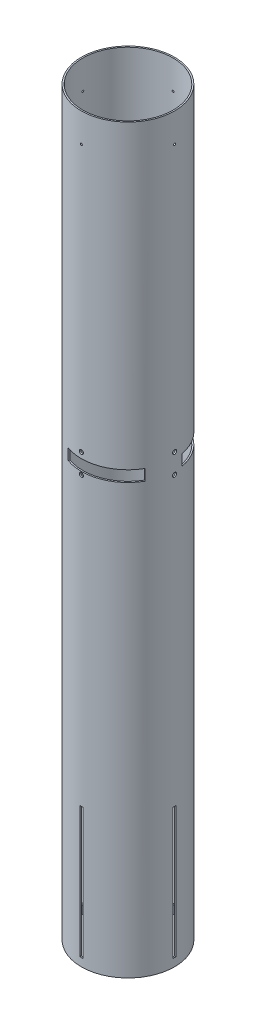
SolidWorks part; units mm, degrees
material "A-Glass Fiber"
ref_plane "Front Plane" through (0, 0, 0) normal (0, 0, 1) x (1, 0, 0)
ref_plane "Top Plane" through (0, 0, 0) normal (0, 1, 0) x (1, 0, 0)
ref_plane "Right Plane" through (0, 0, 0) normal (1, 0, 0) x (0, 0, -1)
sketch "Sketch1" plane through (0, 0, 0) normal (0, 1, 0) x (1, 0, 0)
  circle A0 centre (0, 0) radius 49.53
  circle A1 centre (0, 0) radius 51.1048
  dimension "D1" = 99.06
  dimension "D2" = 102.2096
extrude "Boss-Extrude1" add sketch "Sketch1" along normal blind 812.8
ref_plane "Plane1" through (0, 0, 0) normal (0.7071, 0, 0.7071) x (0.7071, 0, -0.7071)
ref_axis "Axis1" through (0, 812.8, 0) along (0, -1, 0)
sketch "Sketch2" plane through (0, 0, 0) normal (1, 0, 0) x (0, 0, -1)
  line L0 (0, 0) -> (0, 8.89)
  line L1 (1.5875, 8.89) -> (-1.5875, 8.89)
  line L2 (1.5875, 8.89) -> (1.5875, 152.4)
  line L3 (1.5875, 152.4) -> (-1.5875, 152.4)
  line L4 (-1.5875, 8.89) -> (-1.5875, 152.4)
  line L5 (1.5875, 8.89) -> (-1.5875, 152.4) construction
  line L6 (1.5875, 152.4) -> (-1.5875, 8.89) construction
  line L7 (51.1048, 812.8) -> (-51.1048, 812.8) construction
  line L8 (51.1048, 812.8) -> (-51.1048, 812.8)
  line L9 (0, 812.8) -> (0, 488.95)
  line L10 (-51.1048, 0) -> (51.1048, 0) construction
  circle A0 centre (0, 488.95) radius 2.25
  point P0 (0, 80.645)
  dimension "D4" = 4.5
  dimension "D1" = 3.175
  dimension "D5" = 488.95
  dimension "D3" = 152.4
  dimension "D2" = 8.89
extrude "Cut-Extrude1" cut sketch "Sketch2" against normal through all contours L4 L1 L2 L3 region at (0, 80.645, 0)
pattern_circular "CirPattern1" count 4 over 360 about axis through (0, 0, 0) along (0, 1, 0) of "Cut-Extrude1" reverse direction yes
extrude "Cut-Extrude2" cut sketch "Sketch2<3>" against normal through all contours A0 region at (0, 487.404, 1.546)
sketch "Sketch2<3>" plane through (0, 0, 0) normal (1, 0, 0) x (0, 0, -1) same geometry as "Sketch2"
pattern_circular "CirPattern2" count 4 over 360 about axis through (0, 812.8, 0) along (0, -1, 0) of "Cut-Extrude2"
sketch "Sketch3" plane through (0, 0, 0) normal (0.7071, 0, 0.7071) x (0.7071, 0, -0.7071)
  line L0 (0, 0) -> (0, 127) construction
  circle A0 centre (0, 127) radius 3.175
  dimension "D1" = 6.35
  dimension "D2" = 127
extrude "Cut-Extrude3" cut sketch "Sketch3" against normal through all
sketch "Sketch7" plane through (0, 0, 0) normal (0, 1, 0) x (1, 0, 0)
  line L0 (0, 0) -> (-44.2581, -25.5524)
  line L1 (0, 0) -> (0, 93.232) construction
  line L2 (0, 0) -> (-32.8495, 39.1485)
  line L3 (-51.1048, 0) -> (0, 0) construction
  arc A0 (-51.0552, 2.25) -> (-51.0552, -2.25) centre (0, 0) ccw construction
  circle A1 centre (0, 0) radius 49.53 construction
  circle A2 centre (0, 0) radius 51.1048
  circle A3 centre (0, 0) radius 51.1048
  circle A4 centre (0, 0) radius 49.53
  circle A5 centre (0, 0) radius 51.1048 construction
  arc A6 (2.25, 51.0552) -> (-2.25, 51.0552) centre (0, 0) ccw construction
  arc A7 (-51.0552, 2.25) -> (-51.0552, -2.25) centre (0, 0) ccw
  arc A8 (2.25, 51.0552) -> (-2.25, 51.0552) centre (0, 0) ccw
  dimension "D1" = 80
  dimension "D3" = 30
  dimension "D2" = 0
extrude "Cut-Extrude4" cut sketch "Sketch7" against normal blind 12.065 from offset 482.6 contours A4 A3 L0 region at (-43.9137, 0, 24.5741)
pattern_circular "CirPattern3" count 3 over 360 about axis through (0, 812.8, 0) along (0, -1, 0) of "Cut-Extrude4"
pattern_linear "LPattern1" count 2 spacing 21.6916 along (0, -1, 0) of "CirPattern2"
sketch "Sketch8" plane through (0, 0, 0) normal (0, 0, 1) x (1, 0, 0)
  line L0 (49.53, 812.8) -> (-49.53, 812.8) construction
  circle A0 centre (0, 781.05) radius 1.0922
  dimension "D1" = 2.1844
  dimension "D2" = 31.75
extrude "Cut-Extrude5" cut sketch "Sketch8" against normal through all
pattern_circular "CirPattern4" count 4 over 360 about axis through (0, 812.8, 0) along (0, -1, 0) of "Cut-Extrude5"
sketch "Sketch9" plane through (0, 0, 0) normal (0, 0, 1) x (1, 0, 0)
  line L0 (51.1048, 812.8) -> (-51.1048, 812.8) construction
  point P0 (0, 752.856)
  dimension "D1" = 59.944
hole_wizard "1/2 Clearance Hole4" positions "Sketch17" profile "Sketch18" hole size "1/2" standard "ANSI Inch" end condition through all
sketch "Sketch17" plane through (0, 0, 0) normal (0, 0, 1) x (1, 0, 0)
  line L0 (51.1048, 812.8) -> (-51.1048, 812.8) construction
  point P0 (0, 752.856)
  dimension "D1" = 752.856
  dimension "D2" = 59.944
sketch "Sketch18" plane through (0, 752.856, 0) normal (1, 0, 0) x (0, -1, 0)
  line L0 (0, 0) -> (0, 51.1048)
  line L1 (0, 51.1048) -> (6.5481, 51.1048)
  line L2 (6.5481, 51.1048) -> (6.5481, 0)
  line L5 (6.5481, 0) -> (0, 0)
  line L11 (0, -6.35) -> (0, 107.95) construction
  dimension "Thru Hole Dia." = 13.0962
  dimension "Thru Hole Depth" = 51.1048
ref_plane "Plane3" through (24.3888, 0, -29.0654) normal (0.6428, 0, -0.766) x (-0.766, 0, -0.6428)
equation "\"D1@Boss-Extrude1\" = \"Aft_Section_Length\""
equation "\"AB_Coupler_OD_Length\"= 1in"
equation "\"AB_Coupling_Section_Length\"= 0.375in"
equation "\"AB_Coupler_Length\"= \"AB_Coupler_OD_Length\" + \"AB_Coupling_Section_Length\" * 2"
equation "\"AB_Coupler_Num_Screws\"= 4"
equation "\"AB_Coupling_Screw_Diameter\"= 4.5mm"
equation "\"Aft_Section_Length\" = 32in"
equation "\"D4@Sketch2\"=\"AB_Coupling_Screw_Diameter\""
equation "\"D1@CirPattern2\"=\"AB_Coupler_Num_Screws\""
equation "\"Rail_Nut_From_Bottom\"= 5in"
equation "\"Rail_Nut_Diam\"= 0.25in"
equation "\"D1@Sketch3\"=\"Rail_Nut_Diam\""
equation "\"D2@Sketch3\"=\"Rail_Nut_From_Bottom\""
equation "\"AB_BKHD_Thickness\"= 0.375in"
equation "\"AB_Mount_From_Bottom\"= 19.25in"
equation "\"Cutout_Angle\" = 60"
equation "\"Motor_OD\" = 54.4mm"
equation "\"Motor_Length\" = 401mm"
equation "\"Mid_Coupler_Length\" = 12in"
equation "\"AB_Paddle_Height\" = 0.375in"
equation "\"Num_Cutouts\" = 4"
equation "\"AB_Coupler_OD\"= 4.024in"
equation "\"AB_Coupler_ID\"= 3.7in"
equation "\"AB_Coupler_Surface_Diameter\"= 3.899in"
equation "\"AB_Central_Bushing_Length\" = 0.75in"
equation "\"Lead_Screw_Dist\" = 2in"
equation "\"Lead_Screw_Diam\" = 0.375in"
equation "\"Lead_Screw_Length\" = \"Mid_Coupler_Length\" + 2*0.375in + 2*0.5in"
equation "\"Paddle_Pin_Offset\" = 0.25in"
equation "\"Paddle_Pin_Radius\" = 2.25*2/3in"
equation "\"Paddle_Gear_OD\" = 3.2in"
equation "\"Fwd_BKHD_From_Top\" = 18in"
equation "\"Body_Tube_OD\"= 4.024in"
equation "\"Body_Tube_ID\"= 3.90in"
equation "\"Coupler_OD\" = 3.899in"
equation "\"Coupler_ID\" = 3.755in"
equation "\"Fwd_Section_Length\" = 20in"
equation "\"Mid_Section_Length\" = 4in"
equation "\"Aft_Upper_Tube_Length\" = 10in"
equation "\"Aft_Lower_Tube_Length\" = 18in"
equation "\"Nosecone_Coupler_Length\" = 5in"
equation "\"Avionics_Bulkhead_Thickness\" = 0.25in"
equation "\"Avionics_Bulkhead_Lip\" = 0.125in"
equation "\"Avionics_Board_Length\" = \"Mid_Coupler_Length\" - 2*\"Avionics_Bulkhead_Lip\""
equation "\"Lead_Screw_Hole_Diam\" = 0.386in"
equation "\"Centering_Ring_Cutout_Dia\"= 1in"
equation "\"D2@Sketch1\"=\"Body_Tube_OD\""
equation "\"D1@Sketch1\"=\"Body_Tube_ID\""
equation "\"D5@Sketch2\"=\"AB_Mount_From_Bottom\""
equation "\"D19@Cut-Extrude4\"=\"AB_Mount_From_Bottom\"-0.25"
